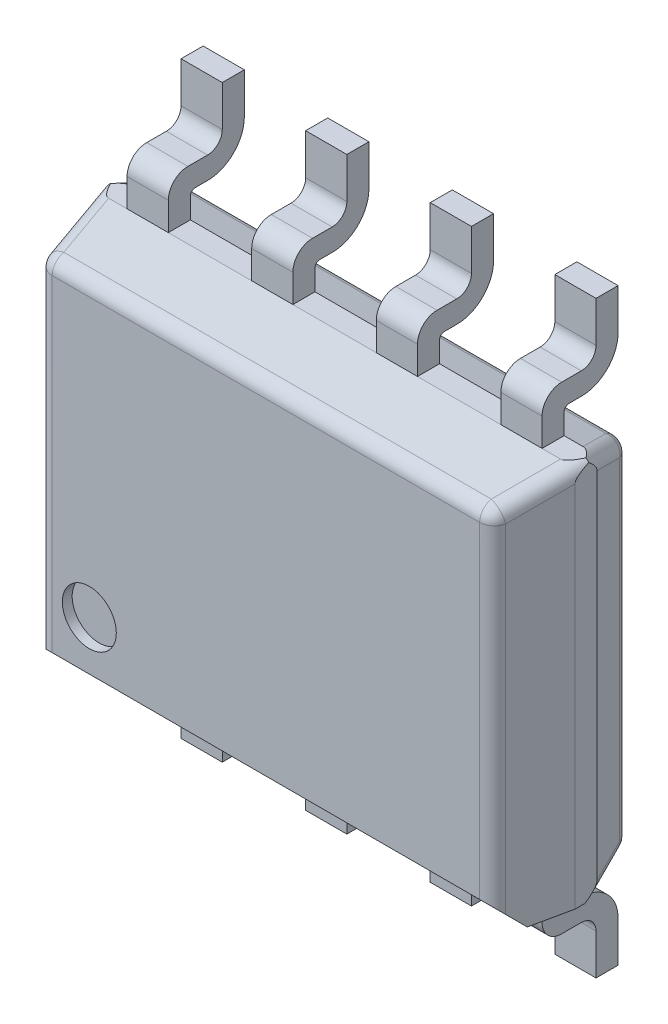
SolidWorks part; units mm, degrees
ref_plane "Front Plane" through (0, 0, 0) normal (0, 0, 1) x (1, 0, 0)
ref_plane "Top Plane" through (0, 0, 0) normal (0, 1, 0) x (1, 0, 0)
ref_plane "Right Plane" through (0, 0, 0) normal (1, 0, 0) x (0, 0, -1)
sketch "Sketch1" plane through (0, 0, 0) normal (0, 0, 1) x (1, 0, 0)
  line L1 (-2.45, 1.95) -> (2.45, 1.95)
  line L2 (-2.45, 1.95) -> (-2.45, -1.95)
  line L3 (-2.45, -1.95) -> (2.45, -1.95)
  line L4 (2.45, 1.95) -> (2.45, -1.95)
  dimension "D1" = 4.9
  dimension "D2" = 3.9
  dimension "D3" = 2.45
  dimension "D4" = 1.95
extrude "Boss-Extrude1" add sketch "Sketch1" along normal blind 1.375
chamfer "Chamfer1" distance 0.3 angle 45 1 edges at (0, -1.95, 1.375)
chamfer "Chamfer2" distance 0.15 distance2 0.45 1 edges at (0, -1.95, 0) first distance on face at (0, 0, 0)
chamfer "Chamfer7" distance 0.15 distance2 0.45 1 edges at (2.45, 0.075, 0) first distance on face at (0, 0.075, 0)
chamfer "Chamfer8" distance 0.15 distance2 0.45 1 edges at (-2.45, 0.075, 0) first distance on face at (-0.075, 0.075, 0)
fillet "Fillet1" radius 0.15 1 edges at (0, -1.8, 0)
chamfer "Chamfer3" distance 0.15 distance2 0.45 1 edges at (0, 1.95, 0) first distance on face at (0, 0.1291, 0)
chamfer "Chamfer6" distance 0.7 distance2 0.15 1 edges at (2.45, 0.15, 1.375) first distance on face at (2.45, -0.33, 0.945)
fillet "Fillet2" radius 0.15 1 edges at (0, 1.8, 0)
chamfer "Chamfer4" distance 0.7 distance2 0.15 1 edges at (-0.075, 1.95, 1.375) first distance on face at (0.46, 1.95, 0.865)
sketch "Sketch2" plane through (0, 0, 1.375) normal (0, 0, 1) x (1, 0, 0)
  line L0 (-2.45, 1.8) -> (-2.45, -1.65) construction
  line L1 (2.3643, -1.95) -> (-2.45, -1.95) construction
  circle A0 centre (-1.8, -1.15) radius 0.275
  dimension "D3" = 0.55
  dimension "D1" = 0.65
  dimension "D2" = 0.8
extrude "Cut-Extrude1" cut sketch "Sketch2" against normal blind 0.1
chamfer "Chamfer5" distance 0.7 distance2 0.15 1 edges at (-2.45, 0.075, 1.375) first distance on face at (-2.45, 0.025, 0.9)
fillet "Fillet3" radius 0.15 1 edges at (0, 1.8, 1.375)
fillet "Fillet4" radius 0.15 3 edges at (-2.3877, 1.8877, 0.9657) (-2.3071, 1.773, 1.3416) (-2.3, 0.0144, 1.375)
fillet "Fillet5" radius 0.15 5 edges at (-2.3921, -1.8921, 0.2763) (-2.3094, -1.7796, 0.0283) (-2.3921, 1.8921, 0.2763) (-2.3094, 1.7796, 0.0283) (-2.3, 0, 0)
fillet "Fillet6" radius 0.15 3 edges at (2.3877, 1.8877, 0.9657) (2.3071, 1.773, 1.3416) (2.3, 0.0144, 1.375)
fillet "Fillet7" radius 0.15 5 edges at (2.3921, 1.8921, 0.2763) (2.3094, 1.7796, 0.0283) (2.3921, -1.8921, 0.2763) (2.3094, -1.7796, 0.0283) (2.3, 0, 0)
ref_plane "Plane1" through (-2.115, 0, 0) normal (-1, 0, 0) x (0, 0, 1)
sketch "Sketch3" plane through (-2.115, 0, 0) normal (-1, 0, 0) x (0, 0, 1)
  line L0 (0.675, 1.95) -> (0.535, 1.95) construction
  line L1 (0.535, 1.95) -> (0.45, 1.95) construction
  line L2 (0.45, -1.95) -> (0.5726, -1.95) construction
  line L3 (0.675, -1.95) -> (0.5726, -1.95) construction
  line L4 (0.675, 1.95) -> (0.535, 1.95)
  line L5 (0.535, 1.95) -> (0.45, 1.95)
  line L6 (0.45, -1.95) -> (0.5726, -1.95)
  line L7 (0.675, -1.95) -> (0.5726, -1.95)
  line L8 (0.675, -1.95) -> (0.45, -1.95)
  line L9 (0.5625, -1.95) -> (0.5625, 1.95) construction
  line L10 (0.5625, 0) -> (0, 0) construction
  line L11 (0.675, 1.95) -> (0.675, 2.235)
  line L12 (0.475, 2.435) -> (0.275, 2.435)
  line L13 (0.125, 2.585) -> (0.125, 3)
  line L14 (0, -1.6919) -> (0, 1.6919) construction
  line L15 (0.45, 1.95) -> (0.45, 2.16)
  line L16 (0.45, 2.21) -> (0.275, 2.21) construction
  line L17 (0.125, 3) -> (-0.1, 3)
  line L18 (0.4, 2.21) -> (0.275, 2.21)
  line L19 (-0.1, 2.585) -> (-0.1, 3)
  line L20 (0.45, 2.175) -> (0.45, 2.21) construction
  line L21 (0.45, 2.175) -> (0.45, 2.175) construction
  line L22 (0.45, 2.175) -> (0.45, 2.175) construction
  arc A0 (0.675, 2.235) -> (0.475, 2.435) centre (0.475, 2.235) ccw
  arc A1 (0.125, 2.585) -> (0.275, 2.435) centre (0.275, 2.585) ccw
  arc A2 (0.45, 2.16) -> (0.4, 2.21) centre (0.4, 2.16) ccw
  arc A3 (-0.1, 2.585) -> (0.275, 2.21) centre (0.275, 2.585) ccw
  arc A4 (0.45, 2.21) -> (0.45, 2.21) centre (0.45, 2.21) ccw construction
  point P20 (0.125, 2.435)
  dimension "D5" = 0.2
  dimension "D6" = 0.15
  dimension "D8" = 0.05
  dimension "D1" = 1.05
  dimension "D2" = 0.565
  dimension "D3" = 0.225
  dimension "D4" = 0.125
  dimension "D7" = 0.225
extrude "Boss-Extrude2" add sketch "Sketch3" against normal blind 0.42 contours L19 A3 L18 A2 L15 L5 L4 L11 A0 L12 A1 L13 L17 region at (-2.115, 2.4356, 0.2471)
mirror "Mirror1" about plane through (0, 0, 0) normal (0, 1, 0) of "Boss-Extrude2"
pattern_linear "LPattern1" count 4 spacing 1.27 along (1, 0, 0) of "Mirror1", "Boss-Extrude2"
